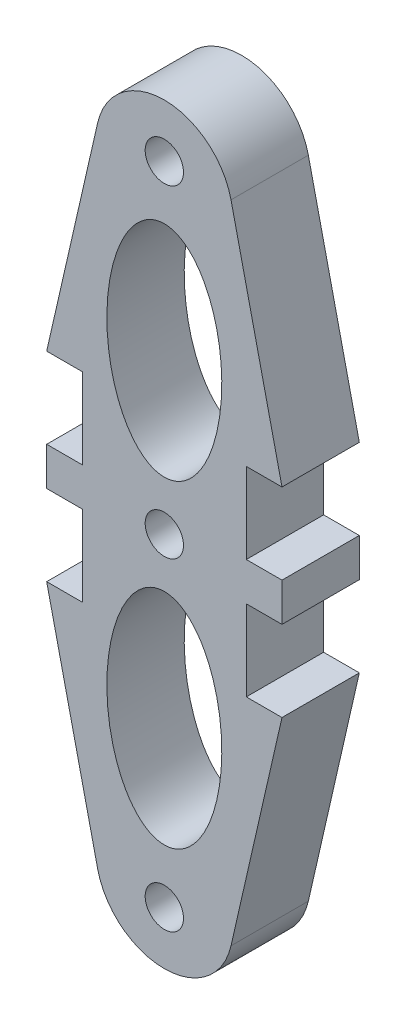
SolidWorks part; units mm, degrees
material "Acrylic (Medium-high impact)"
ref_plane "Front Plane" through (0, 0, 0) normal (0, 0, 1) x (1, 0, 0)
ref_plane "Top Plane" through (0, 0, 0) normal (0, 1, 0) x (1, 0, 0)
ref_plane "Right Plane" through (0, 0, 0) normal (1, 0, 0) x (0, 0, -1)
sketch "Sketch1" plane through (0, 0, 0) normal (0, 0, 1) x (1, 0, 0)
  line L0 (-213.0416, 464.8524) -> (49786.9584, 464.8524) construction
  line L1 (781.4592, 464.8524) -> (778.7592, 464.8524)
  line L2 (781.4592, 464.8524) -> (781.4592, 470.9524)
  line L3 (781.4592, 470.9524) -> (778.7592, 470.9524)
  line L4 (787.6592, -515.9255) -> (787.6592, 49484.0745) construction
  line L5 (-215.2216, 463.4024) -> (49784.7784, 463.4024) construction
  line L6 (793.8592, 470.9524) -> (793.8592, 487.8374) construction
  line L7 (-217.5077, 461.9524) -> (49782.4923, 461.9524) construction
  line L8 (786.2092, -537.0976) -> (786.2092, 49462.9024) construction
  line L9 (789.1092, -536.5976) -> (789.1092, 49463.4024) construction
  line L10 (793.8592, 464.8524) -> (796.5592, 464.8524)
  line L11 (781.4592, 470.9524) -> (793.8592, 470.9524) construction
  line L12 (793.8592, 470.9524) -> (796.5592, 470.9524)
  line L13 (793.8592, 464.8524) -> (793.8592, 470.9524)
  line L14 (778.7592, 464.8524) -> (778.7592, 461.9524)
  line L15 (796.5592, 464.8524) -> (796.5592, 461.9524)
  line L16 (786.2092, 487.8374) -> (782.615, 487.8374) construction
  line L17 (781.4592, 461.9524) -> (778.7592, 461.9524)
  line L18 (793.8592, 470.9524) -> (793.1379, 470.9192) construction
  line L19 (781.4592, 455.8524) -> (778.7592, 455.8524)
  line L20 (781.4592, 461.9524) -> (781.4592, 455.8524)
  line L21 (793.8592, 461.9524) -> (796.5592, 461.9524)
  line L22 (793.8592, 461.9524) -> (793.8592, 455.8524)
  line L23 (793.8592, 455.8524) -> (796.5592, 455.8524)
  line L24 (778.7592, 470.9524) -> (782.615, 487.8374)
  line L25 (792.7033, 487.8374) -> (796.5592, 470.9524)
  line L26 (792.7033, 438.9674) -> (796.5592, 455.8524)
  line L27 (789.1092, 438.9674) -> (792.7033, 438.9674) construction
  line L28 (786.2092, 438.9674) -> (782.615, 438.9674) construction
  line L29 (778.7592, 455.8524) -> (782.615, 438.9674)
  line L35 (789.1092, 487.8374) -> (792.7033, 487.8374) construction
  arc A0 (782.615, 487.8374) -> (792.7033, 487.8374) centre (787.6592, 486.6855) cw
  arc A1 (782.615, 438.9674) -> (792.7033, 438.9674) centre (787.6592, 440.1192) ccw
  circle A3 centre (787.6592, 487.8374) radius 1.45
  circle A5 centre (787.6592, 438.9674) radius 1.45
  circle A6 centre (787.6592, 463.4024) radius 1.45
  ellipse E0 centre (787.6592, 475.4481) end of major axis (787.6592, 483.7502) minor radius 4.3465
  ellipse E1 centre (787.6592, 451.3566) end of major axis (787.6592, 443.0545) minor radius 4.3465
  point P10 (778.7592, 463.4024)
  point P19 (796.5592, 463.4024)
  dimension "D1" = 2.9
  dimension "D3" = 6.1
  dimension "D10" = 5.174
  dimension "D2" = 2.7
  dimension "D4" = 24.435
  dimension "D5" = 12.4
  dimension "D6" = 16.6042
  dimension "D7" = 8.693
  dimension "D8" = 2.2937
extrude "Boss-Extrude1" add sketch "Sketch1" along normal blind 5.85 contours L3 A3 A5 region at (782.0555, 467.9024, 0)
